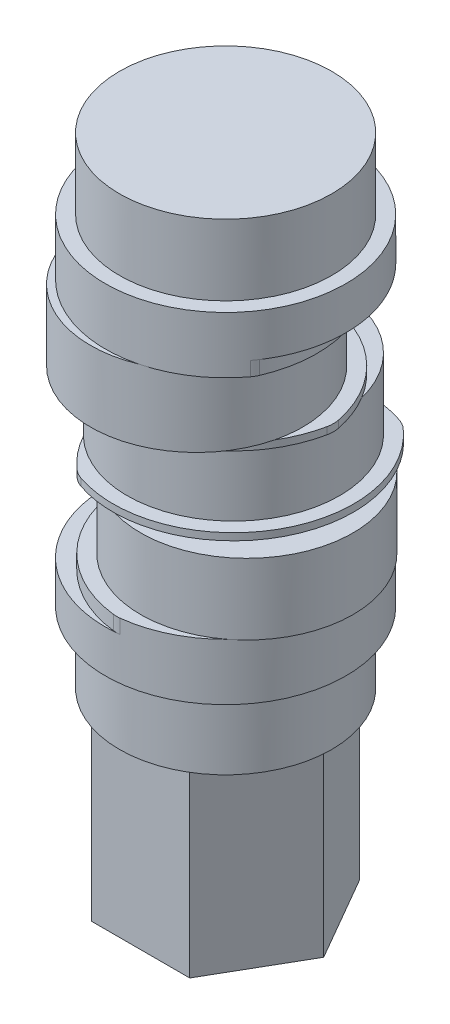
SolidWorks part; units mm, degrees
ref_plane "Front Plane" through (0, 0, 0) normal (0, 0, 1) x (1, 0, 0)
ref_plane "Top Plane" through (0, 0, 0) normal (0, 1, 0) x (1, 0, 0)
ref_plane "Right Plane" through (0, 0, 0) normal (1, 0, 0) x (0, 0, -1)
sketch "Sketch3" plane through (0, 0, 0) normal (0, 1, 0) x (1, 0, 0)
  line L0 (-0.75, 1.299) -> (0, 0) construction
  line L1 (0, 0) -> (-0.75, -1.299) construction
  line L2 (0, 0) -> (1.5, 0) construction
  circle A0 centre (0, 0) radius 1.5 construction
  circle A1 centre (1.5, 0) radius 8.5
  circle A2 centre (-0.75, 1.299) radius 8.5
  circle A3 centre (-0.75, -1.299) radius 8.5
  dimension "D1" = 3
  dimension "D2" = 17
  dimension "D3" = 120
  dimension "D4" = 120
sketch "Sketch4" plane through (0, 0, 0) normal (0, 1, 0) x (1, 0, 0)
  line L1 (-3.4641, 6) -> (-6.9282, 0)
  line L2 (-6.9282, 0) -> (-3.4641, -6)
  line L3 (-3.4641, -6) -> (3.4641, -6)
  line L4 (3.4641, -6) -> (6.9282, 0)
  line L5 (6.9282, 0) -> (3.4641, 6)
  line L6 (3.4641, 6) -> (-3.4641, 6)
  circle A0 centre (0, 0) radius 6 construction
  dimension "D1" = 12
extrude "Boss-Extrude1" add sketch "Sketch4" along normal blind 13
sketch "Sketch5" plane through (0, 13, 0) normal (0, 1, 0) x (1, 0, 0)
  circle A0 centre (0, 0) radius 7.5
  dimension "D1" = 15
extrude "Boss-Extrude2" add sketch "Sketch5" along normal blind 8
sketch "Sketch6" plane through (0, 21, 0) normal (0, 1, 0) x (1, 0, 0)
  circle A0 centre (0, 0) radius 8.5
  circle A1 centre (1.5, 0) radius 8.5
  circle M1 centre (0, 0) radius 7.5
  dimension "D1" = 17
extrude "Boss-Extrude3" add sketch "Sketch6" along normal blind 1 contours A1 M1 | A0 A1 M1 region at (6.1121, 21, 5.5946) region at (0.1719, 21, 0)
sketch "Sketch7" plane through (0, 22, 0) normal (0, 1, 0) x (1, 0, 0)
  circle A0 centre (1.5, 0) radius 7.5
  arc A1 (-4.5833, 5.9366) -> (-4.5833, -5.9366) centre (0, 0) ccw construction
extrude "Boss-Extrude4" add sketch "Sketch7" along normal blind 5
sketch "Sketch8" plane through (0, 27, 0) normal (0, 1, 0) x (1, 0, 0)
  circle A0 centre (1.5, 0) radius 8.5
  circle A1 centre (-0.75, 1.299) radius 8.5
  circle A2 centre (1.5, 0) radius 8.5 construction
  circle M1 centre (1.5, 0) radius 7.5
extrude "Boss-Extrude5" add sketch "Sketch8" along normal blind 0.5 contours A1 M1 | A1 A0 M1 region at (5.5922, 27, -6.6403) region at (0.8921, 27, -0.3509)
sketch "Sketch9" plane through (0, 27.5, 0) normal (0, 1, 0) x (1, 0, 0)
  circle A0 centre (-0.75, 1.299) radius 7.5
  arc A1 (-0.6012, -7.1997) -> (6.6845, 5.4195) centre (1.5, 0) ccw construction
extrude "Boss-Extrude6" add sketch "Sketch9" along normal blind 5
sketch "Sketch11" plane through (0, 32.5, 0) normal (0, 1, 0) x (1, 0, 0)
  circle A0 centre (-0.75, 1.299) radius 8.5
  circle A1 centre (-0.75, -1.299) radius 8.5
  arc A2 (-3.8251, -6.6252) -> (4.5751, 7.9243) centre (-0.75, 1.299) ccw construction
  circle M1 centre (-0.75, 1.299) radius 7.5
extrude "Boss-Extrude7" add sketch "Sketch11" along normal blind 0.5 contours A1 M1 | A0 A1 M1 region at (-8.5574, 32.5, -1.5267) region at (-0.75, 32.5, -0.5972)
sketch "Sketch12" plane through (0, 33, 0) normal (0, 1, 0) x (1, 0, 0)
  circle A0 centre (-0.75, -1.299) radius 7.5
  arc A1 (6.5357, 3.0792) -> (-8.0357, 3.0792) centre (-0.75, 1.299) ccw construction
extrude "Boss-Extrude8" add sketch "Sketch12" along normal blind 5
sketch "Sketch13" plane through (0, 38, 0) normal (0, 1, 0) x (1, 0, 0)
  circle A0 centre (-0.75, -1.299) radius 8.5
  circle A1 centre (0, 0) radius 8.5
  arc A3 (7.6501, 0) -> (-9.1501, 0) centre (-0.75, -1.299) ccw construction
  circle M1 centre (-0.75, -1.299) radius 7.5
extrude "Boss-Extrude9" add sketch "Sketch13" along normal blind 1 contours A1 M1 | A1 A0 M1 region at (7.3307, 38, 3.0859) region at (-0.664, 38, 1.1501)
sketch "Sketch14" plane through (0, 39, 0) normal (0, 1, 0) x (1, 0, 0)
  circle A0 centre (0, 0) radius 7.5
  arc A1 (6.5357, 3.0792) -> (-8.0357, 3.0792) centre (-0.75, 1.299) ccw construction
extrude "Boss-Extrude10" add sketch "Sketch14" along normal blind 8
fillet "Fillet1" radius 2 8 edges at (0.75, 21.5, -8.4668) (0.75, 21.5, 8.4668) (-3.8251, 27.25, 6.6252) (4.5751, 27.25, -7.9243) (7.6501, 32.75, 0) (-9.1501, 32.75, 0) (-7.7075, 38.5, -3.5839) (6.9575, 38.5, 4.8829)
sketch "Sketch15" plane through (0, 21, 0) normal (0, -1, 0) x (1, 0, 0)
  circle A0 centre (0, 0) radius 8.5
  dimension "D1" = 17
extrude "Boss-Extrude11" add sketch "Sketch15" along normal blind 3
sketch "Sketch16" plane through (0, 39, 0) normal (0, -1, 0) x (1, 0, 0)
  circle A0 centre (0, 0) radius 8.5
  dimension "D1" = 17
extrude "Boss-Extrude12" add sketch "Sketch16" against normal blind 3
equation "\"N_pin\"= 24"
equation "\"R_pin\"= 60"
equation "\"d_pin\"= 13"
equation "\"e\"= 1.5"
equation "\"t_disk\"= 5"
equation "\"N_outpin\"= 8"
equation "\"R_outpin\"= 34"
equation "\"d_outpin\"= 13"
equation "\"N_lobes\"= \"N_pin\" - 1"
equation "\"d_outhole\"= \"d_outpin\" + 2 * \"e\""
equation "\"ratio\"= \"N_lobes\""
equation "\"d_center\"= 24"
equation "\"a_hole1\"= 0 / \"N_lobes\""
equation "\"a_hole2\"= 360 / \"N_disk\" / \"N_lobes\""
equation "\"a_hole3\"= 720 / \"N_disk\" / \"N_lobes\""
equation "\"N_disk\"= 3"
equation "\"t_gap\"= 0.5"
equation "\"L_stack\"= \"N_disk\" * \"t_disk\" + (\"N_disk\" - 1) * \"t_gap\""
equation "\"d_pinshaft\"= 6"
equation "\"d_ecc\"= 15"
equation "\"d_outbrg\"= 47"
equation "\"w_outbrg\"= 7"
equation "\"d_outshaft\"= 35"
equation "\"w_brg\"= 5"
equation "\"D1@Boss-Extrude5\"=\"t_gap\""
equation "\"D1@Boss-Extrude7\"=\"t_gap\""
equation "\"c_run\"= 0.5"
equation "\"c_ax\"= 2 * \"t_gap\""
equation "\"D_pocket\"= 2 * \"R_pin\" + \"d_pin\" + 2 * \"c_run\""
equation "\"h_pocket\"= \"L_stack\" + 2 * \"c_ax\""
equation "\"t_floor\"= 8"
equation "\"d_insert\"= 5.6"
equation "\"N_bolt\"= 8"
equation "\"R_bolt\"= \"D_pocket\" / 2 + 2 + \"d_insert\" / 2"
equation "\"D_housing\"= 2 * (\"R_bolt\" + \"d_insert\" / 2 + 2.5)"
equation "\"D1@Boss-Extrude2\"=\"t_floor\""
equation "\"D1@Sketch5\"=\"d_ecc\""
equation "\"D1@Boss-Extrude10\"=\"t_floor\""
equation "\"D1@Boss-Extrude8\"=\"w_brg\""
equation "\"D1@Boss-Extrude6\"=\"w_brg\""
equation "\"D1@Boss-Extrude4\"=\"w_brg\""
equation "\"D1@Sketch6\"=\"d_ecc\"+2"
equation "\"D1@Sketch15\"=\"d_ecc\"+2"
equation "\"D1@Boss-Extrude11\"=\"t_floor\"-\"w_brg\""
equation "\"D1@Boss-Extrude3\"=\"t_gap\"*2"
equation "\"D1@Boss-Extrude9\"=\"t_gap\"*2"
equation "\"D1@Sketch16\"=\"d_ecc\"+2"
equation "\"D1@Boss-Extrude12\"=\"t_floor\"-\"w_brg\""
